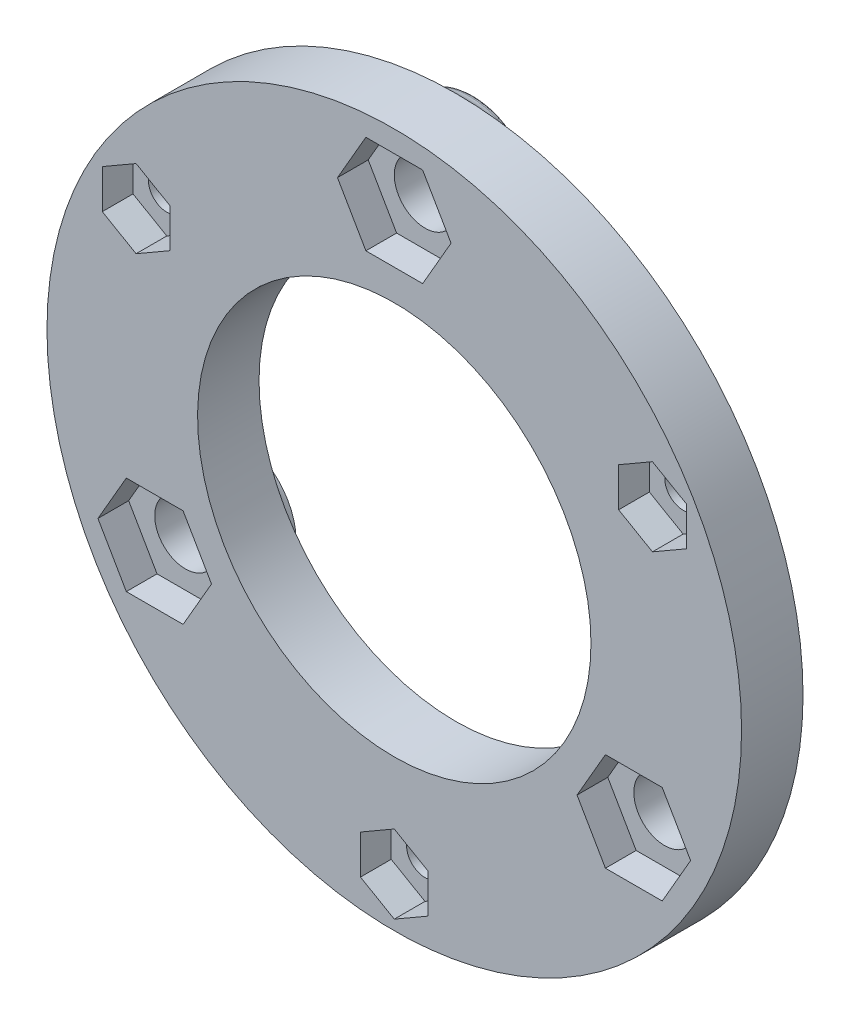
SolidWorks part; units mm, degrees
material "PLA"
ref_plane "Front Plane" through (0, 0, 0) normal (0, 0, 1) x (1, 0, 0)
ref_plane "Top Plane" through (0, 0, 0) normal (0, 1, 0) x (1, 0, 0)
ref_plane "Right Plane" through (0, 0, 0) normal (1, 0, 0) x (0, 0, -1)
sketch "Sketch2" plane through (0, 0, 0) normal (0, 0, 1) x (1, 0, 0)
  line L0 (0, 22.5) -> (0, 0) construction
  line L1 (0, 0) -> (21.0011, 12.125) construction
  circle A0 centre (0, 0) radius 28.25
  circle A1 centre (0, 0) radius 16
  circle A2 centre (0, 0) radius 22.5 construction
  circle A3 centre (0, 22.5) radius 2.5
  circle A4 centre (0, 0) radius 24.25 construction
  circle A5 centre (19.4856, -11.25) radius 2.5
  circle A8 centre (21.0011, 12.125) radius 1.5
  circle A9 centre (0, -24.25) radius 1.5
  circle A11 centre (0, 0) radius 6.25 construction
  circle A14 centre (0, 22.5) radius 5 construction
  circle A15 centre (0, 0) radius 17.5 construction
  circle A16 centre (-19.4856, -11.25) radius 2.5
  circle A19 centre (-21.0011, 12.125) radius 1.5
  point P17 (0, 0)
  point P24 (0, 0)
  dimension "D1" = 56.5
  dimension "D2" = 45
  dimension "D4" = 5
  dimension "D7" = 3
  dimension "D3" = 12.5
  dimension "D10" = 10
  dimension "D5" = 4
  dimension "D9" = 1.5
  dimension "D11" = 60
  dimension "D6" = 3
  dimension "D8" = 3
extrude "Boss-Extrude1" add sketch "Sketch2" along normal blind 5
sketch "Sketch3" plane through (0, 0, 5) normal (0, 0, 1) x (1, 0, 0)
  line L0 (0, 22.5) -> (0, 0) construction
  line L13 (-4.6188, 22.5) -> (-2.3094, 18.5) construction
  line L14 (-2.3094, 18.5) -> (2.3094, 18.5) construction
  line L15 (2.3094, 18.5) -> (4.6188, 22.5) construction
  line L16 (4.6188, 22.5) -> (2.3094, 26.5) construction
  line L17 (2.3094, 26.5) -> (-2.3094, 26.5) construction
  line L18 (-2.3094, 26.5) -> (-4.6188, 22.5) construction
  line L19 (4.6188, 22.5) -> (2.3094, 26.5)
  line L20 (21.0011, 8.9496) -> (23.7511, 10.5373) construction
  line L21 (23.7511, 10.5373) -> (23.7511, 13.7127) construction
  line L22 (23.7511, 13.7127) -> (21.0011, 15.3004) construction
  line L23 (21.0011, 15.3004) -> (18.2511, 13.7127) construction
  line L24 (18.2511, 13.7127) -> (18.2511, 10.5373) construction
  line L25 (18.2511, 10.5373) -> (21.0011, 8.9496) construction
  line L26 (2.3094, 26.5) -> (-2.3094, 26.5)
  line L27 (-2.3094, 26.5) -> (-4.6188, 22.5)
  line L28 (-4.6188, 22.5) -> (-2.3094, 18.5)
  line L29 (-2.3094, 18.5) -> (2.3094, 18.5)
  line L30 (2.3094, 18.5) -> (4.6188, 22.5)
  line L31 (23.7511, 13.7127) -> (21.0011, 15.3004)
  line L32 (21.0011, 15.3004) -> (18.2511, 13.7127)
  line L33 (18.2511, 13.7127) -> (18.2511, 10.5373)
  line L34 (18.2511, 10.5373) -> (21.0011, 8.9496)
  line L35 (21.0011, 8.9496) -> (23.7511, 10.5373)
  line L36 (23.7511, 10.5373) -> (23.7511, 13.7127)
  circle A0 centre (0, 22.5) radius 4 construction
  circle A1 centre (21.0011, 12.125) radius 2.75 construction
  dimension "D1" = 8
  dimension "D2" = 5.5
extrude "Cut-Extrude1" cut sketch "Sketch3" against normal blind 2.5
pattern_circular "CirPattern1" count 3 over 360 about axis through (0, 0, 5) along (0, 0, -1) of "Cut-Extrude1" reverse direction yes
sketch "Sketch4" plane through (0, 0, 0) normal (0, 0, -1) x (-1, 0, 0)
  circle A0 centre (0, 22.5) radius 4
  circle A1 centre (0, 22.5) radius 5
  dimension "D1" = 8
extrude "Boss-Extrude2" add sketch "Sketch4" along normal blind 1.5
fillet "Fillet1" radius 1.5 1 edges at (5, 22.5, 0)
fillet "Fillet2" radius 0.5 2 edges at (0, 27.5, -1.5) (0, 17.5, -1.5)
chamfer "Chamfer1" distance 0.25 angle 45 1 edges at (-4, 22.5, -1.5)
pattern_circular "CirPattern2" count 3 over 360 about axis through (0, 0, 5) along (0, 0, -1) of "Fillet1", "Boss-Extrude2", "Chamfer1" reverse direction yes
equation "\"Nr\"= 155"
equation "\"module\"= 0.5"
equation "\"pressure_angle\"= 20.0deg"
equation "\"h_a\"= 0.5"
equation "\"h_f\"= 0.625"
equation "\"clr_tip_root\"= 0.125"
equation "\"dp_r\"= 77.5"
equation "\"db_r\"= 72.8261781109079"
equation "\"fw_r\"= 22.13479809822934"
equation "\"alpha_r\"= 0.8539582918412449"
equation "\"beta_r\"= 2.869206906263135"
equation "\"bearing_ID\"= 55"
equation "\"bearing_OD\"= 72"
equation "\"bearing_height\"= 9"
equation "\"clearance_planet\"= 1.5"
equation "\"case_dist\"= 6.5"
equation "\"Motor_case_OD_max\"= 112.3"
equation "\"case_mounting_PCD\"= 104.8"
equation "\"bearing mount thickness\"= 8"
equation "\"case_mounting_hole_dia\"= 3"
equation "\"output_mounting_PCD\"= 80"
equation "\"output_mounting_hole_dia\"= 4"
equation "\"clearance_case_mount_holes_shell_thickness\"= 1"
equation "\"motor_case_OD_base\"= 102.8"
equation "\"sec_carrier_thickness\"= 5"
equation "\"sun_coupler_hub_thickness\"= 4"
equation "\"clearance_sun_coupler_sec_carrier\"= 1.5"
equation "\"clearance_motor_and_case\"= 5"
equation "\"motor_OD\"= 87.8"
equation "\"Motor_case_thickness\"= 2.5"
equation "\"Motor_case_ID\"= 97.8"
equation "\"case_mounting_hole_shift\"= 1.0"
equation "\"output_mounting_nut_wrench_size\"= 7"
equation "\"output_mounting_nut_thickness\"= 3.2"
equation "\"case_mounting_hole_allen_socket_dia\"= 5.5"
equation "\"output_mounting_nut_depth\"= 3"
equation "\"case_mounting_bolt_depth\"= 4.5"
equation "\"Ns\"= 25"
equation "\"Np\"= 65"
equation "\"ring_radial_thickness\"= 5.0"
equation "\"ring_OD\"= 87.5"
equation "\"ring_to_chamfer_clearance\"= 2"
equation "\"Motor_case_OD_base_to_chamfer\"= 5"
equation "\"pattern_offset_from_motor_case_OD_base\"= 3"
equation "\"pattern_bulge_dia\"= 3"
equation "\"pattern_num_bulge\"= 18"
equation "\"pattern_depth\"= 2"
equation "\"motor_height\"= 31.5"
equation "\"case_mounting_wrench_size\"= 5.5"
equation "\"case_mounting_nut_clearance\"= 2"
equation "\"base_plate_thickness\"= 4"
equation "\"case_mounting_nut_thickness\"= 2.4"
equation "\"case_mounting_surface_height\"= 4"
equation "\"motor_mount_hole_PCD\"= 36"
equation "\"motor_mount_hole_dia\"= 4"
equation "\"motor_mount_hole_num\"= 4"
equation "\"central_hole_offset_from_motor_mount_PCD\"= 5"
equation "\"wire_slot_dist_from_center\"= 40"
equation "\"wire_slot_length\"= 10"
equation "\"wire_slot_radius\"= 2.5"
equation "\"driver_upper_holes_dist_from_center\"= 29"
equation "\"driver_lower_holes_dist_from_center\"= 13"
equation "\"driver_side_holes_dist_from_center\"= 22.5"
equation "\"driver_mount_holes_dia\"= 3"
equation "\"driver_mount_inserts_OD\"= 4.8"
equation "\"driver_mount_thickness\"= 1.5"
equation "\"driver_mount_height\"= 6"
equation "\"air_flow_hole_offset\"= 3"
equation "\"num_planet\"= 3"
equation "\"planet_pin_bolt_dia\"= 5"
equation "\"planet_pin_socket_head_dia\"= 8.5"
equation "\"carrier_PCD\"= 45.0"
equation "\"D1@Sketch2\"=\"bearing_ID\" + \"standard_fillet_1_5mm\""
equation "\"D2@Sketch2\"=\"carrier_PCD\""
equation "\"D4@Sketch2\"=\"planet_pin_bolt_dia\""
equation "\"D6@Sketch2\"=\"num_planet\""
equation "\"D8@Sketch2\"=\"num_planet\""
equation "\"D1@CirPattern1\"=\"num_planet\""
equation "\"planet_shaft_dia\"= 8"
equation "\"fw_p\"= 22.13479809822934"
equation "\"planet_shaft_step_offset\"= 1"
equation "\"carrier_trapezoidal_support_sun_offset\"= 5"
equation "\"carrier_trapezoidal_support_hole_PCD_offset_bearing_ID\"= 4"
equation "\"carrier_trapezoidal_support_hole_dia\"= 3"
equation "\"carrier_trapezoidal_support_hole_socket_head_dia\"= 5.5"
equation "\"carrier_bearing_step_width\"= 1.5"
equation "\"standard_clearance_1_5mm\"= 1.5"
equation "\"standard_fillet_1_5mm\"= 1.5"
equation "\"sun_shaft_bearing_OD\"= 16"
equation "\"sun_shaft_bearing_width\"= 5"
equation "\"standard_bearing_insertion_chamfer\"= 0.5"
equation "\"D7@Sketch2\"=\"carrier_trapezoidal_support_hole_dia\""
equation "\"D5@Sketch2\"=\"carrier_trapezoidal_support_hole_PCD_offset_bearing_ID\""
equation "\"D3@Sketch2\"=\"Ns\"*\"module\""
equation "\"carrier_trapezoidal_support_hole_wrench_size\"= 5.5"
equation "\"planet_pin_bolt_wrench_size\"= 8"
equation "\"D1@Boss-Extrude1\"=\"sec_carrier_thickness\""
equation "\"D1@Cut-Extrude1\"=\"sec_carrier_thickness\"/2"
equation "\"D1@Sketch4\"=\"planet_shaft_dia\""
equation "\"D2@Sketch4\"=\"planet_shaft_step_offset\""
equation "\"D1@Boss-Extrude2\"=\"clearance_planet\""
equation "\"D1@Fillet1\"=\"standard_fillet_1_5mm\""
equation "\"D1@Chamfer1\"=\"standard_bearing_insertion_chamfer\"/2"
equation "\"D1@Fillet2\"=\"standard_fillet_1_5mm\"/3"
equation "\"D1@CirPattern2\"=\"num_planet\""
equation "\"D10@Sketch2\"=\"planet_shaft_dia\"+\"planet_shaft_step_offset\"*2"
equation "\"D9@Sketch2\"=\"standard_clearance_1_5mm\""
equation "\"D1@Sketch3\"=\"planet_pin_bolt_wrench_size\""
equation "\"D11@Sketch2\"=180/\"num_planet\""
equation "\"D2@Sketch3\"=\"carrier_trapezoidal_support_hole_wrench_size\""
equation "\"pressure angle\"= 20.0deg"
equation "\"motor_output_hole_PCD\"= 23"
equation "\"motor_output_hole_dia\"= 4"
equation "\"motor_output_hole_num\"= 4"
equation "\"h_b\"= 0.625"
equation "\"dp_s\"= 12.5"
equation "\"db_s\"= 11.746157759823856"
equation "\"fw_s_calc\"= 22.13479809822934"
equation "\"alpha_s\"= 0.8539582918412449"
equation "\"beta_s\"= 5.49208341631751"
equation "\"dp_p\"= 32.5"
equation "\"db_p\"= 30.540010175542022"
equation "\"alpha_p\"= 0.8539582918412485"
equation "\"beta_p\"= 1.0613141855482722"
equation "\"planet_bearing_OD\"= 12"
equation "\"planet_bearing_width\"= 3.5"
equation "\"planet_bore\"= 10"
equation "\"sun_shaft_bearing_ID\"= 8"
equation "\"sun_hub_dia\"= 33.0"
equation "\"sun_central_bolt_dia\"= 5"
equation "\"sun_central_bolt_socket_head_dia\"= 8.5"
equation "\"fw_s_used\"= 30.13479809822934"
equation "\"motor_output_hole_CSK_OD\"= 8"
equation "\"motor_output_hole_CSK_head_height\"= 2.0"
equation "\"bearing_retainer_thickness\"= 2"
equation "\"tight_clearance_3DP\" = 0.4"
equation "\"loose_clearance_3DP\" = 0.8"
